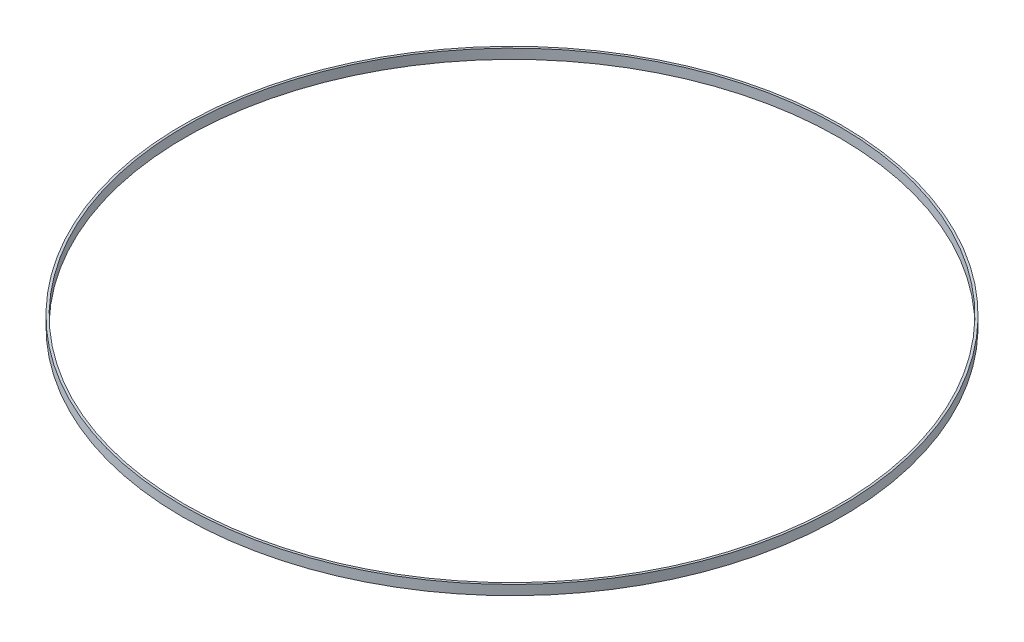
SolidWorks part; units mm, degrees
ref_plane "Front Plane" through (0, 0, 0) normal (0, 0, 1) x (1, 0, 0)
ref_plane "Top Plane" through (0, 0, 0) normal (0, 1, 0) x (1, 0, 0)
ref_plane "Right Plane" through (0, 0, 0) normal (1, 0, 0) x (0, 0, -1)
ref_axis "Axis1" through (0, -55, 0) along (0, 1, 0)
sketch "Sketch1" plane through (0, 0, 0) normal (0, 1, 0) x (1, 0, 0)
  circle A0 centre (0, 0) radius 440
  circle A1 centre (0, 0) radius 437
extrude "Boss-Extrude1" add sketch "Sketch1" along normal blind 13
